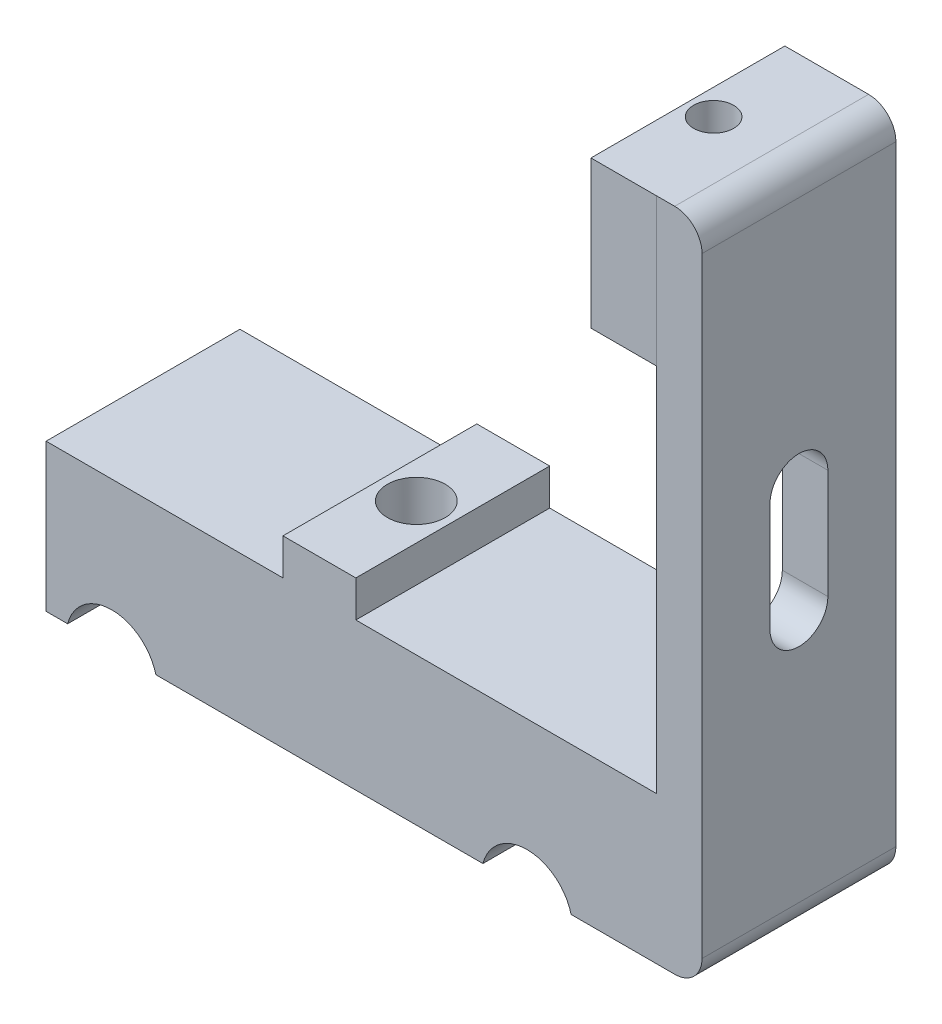
SolidWorks part; units mm, degrees
ref_plane "Front Plane" through (0, 0, 0) normal (0, 0, 1) x (1, 0, 0)
ref_plane "Top Plane" through (0, 0, 0) normal (0, 1, 0) x (1, 0, 0)
ref_plane "Right Plane" through (0, 0, 0) normal (1, 0, 0) x (0, 0, -1)
sketch "Sketch2" plane through (0, 0, 0) normal (0, 0, 1) x (1, 0, 0)
  line L0 (10.1, 0) -> (-10.1, 0)
  line L1 (-10.1, 0) -> (-10.1, 1.7099)
  line L2 (-10.1, 1.7099) -> (-6.2548, 7)
  line L3 (-6.2548, 7) -> (6.2548, 7)
  line L4 (0, 7) -> (0, 0)
  line L5 (0, 0) -> (0, 9.2516) construction
  line L6 (10.1, 1.7099) -> (6.2548, 7)
  line L7 (10.1, 0) -> (10.1, 1.7099)
  dimension "D1" = 20.2
  dimension "D2" = 7
extrude "Boss-Extrude1" add sketch "Sketch2" along normal blind 10.8 contours L4 L3 L2 L1 L0 | L0 L7 L6 L3 L4 region at (4.4168, 3.2082, 0) region at (-4.4168, 3.2082, 0)
sketch "Sketch4" plane through (0, 0, 0) normal (0, 0, 1) x (1, 0, 0)
  line L0 (-4, 0) -> (-4, -4.8)
  line L1 (10.1, 0) -> (-10.1, 0) construction
  line L2 (-4, -4.8) -> (-30, -4.8)
  line L3 (-30, -4.8) -> (-30, -29.8)
  line L4 (-30, -29.8) -> (30, -29.8)
  line L5 (0, 0) -> (0, -29.8) construction
  line L6 (0, -29.8) -> (0, 0)
  line L7 (4, 0) -> (-4, 0)
  line L8 (0, 0) -> (0, -30.5381) construction
  line L9 (30, -4.8) -> (30, -29.8)
  line L10 (4, -4.8) -> (30, -4.8)
  line L11 (4, 0) -> (4, -4.8)
  line L13 (-30, -20.98) -> (30, -20.98)
  line L14 (-30, -20.98) -> (-30, -23.48)
  line L15 (-30, -23.48) -> (30, -23.48)
  line L16 (30, -20.98) -> (30, -23.48)
  dimension "D1" = 4.8
  dimension "D2" = 4
  dimension "D3" = 25
  dimension "D4" = 60
  dimension "D6" = 8.82
extrude "Boss-Extrude2" add sketch "Sketch4" along normal mid plane 21.28 contours L6 L7 L0 L2 L3 L4 | L11 L7 L6 L4 L9 L10 region at (-14.5054, -12.4909, 0) region at (14.5054, -12.4909, 0)
sketch "Sketch5" plane through (0, 0, 0) normal (0, 0, 1) x (1, 0, 0)
  line L0 (-29.791, -22.2274) -> (26.9734, -22.2274) construction
  line L3 (0, -20.98) -> (0, 7) construction
  line L5 (-6.2548, 7) -> (6.2548, 7) construction
  line L20 (-30, -20.98) -> (30, -20.98) construction
  circle A0 centre (-22.791, -22.2274) radius 5
  circle A1 centre (22.791, -22.2274) radius 5
  dimension "D1" = 7
extrude "Cut-Extrude1" cut sketch "Sketch5" along normal through all both and the other way through all
fillet "Fillet1" radius 1 6 edges at (-10.1, 0, 5.4) (-10.1, 1.7099, 5.4) (-6.2548, 7, 5.4) (6.2548, 7, 5.4) (10.1, 0, 5.4) (10.1, 1.7099, 5.4)
sketch "Sketch6" plane through (30, 0, 0) normal (1, 0, 0) x (0, 0, -1)
  line L0 (-10.64, -20.98) -> (10.64, -20.98) construction
  line L1 (-10.64, -4.8) -> (10.64, -4.8)
  line L2 (-10.64, -4.8) -> (-10.64, -20.98)
  line L3 (-10.64, -20.98) -> (10.64, -20.98)
  line L4 (10.64, -4.8) -> (10.64, -20.98)
extrude "Boss-Extrude3" add sketch "Sketch6" along normal blind 12
sketch "Sketch7" plane through (0, -4.8, 0) normal (0, 1, 0) x (1, 0, 0)
  line L0 (4, -10.64) -> (42, -10.64) construction
  line L1 (42, 10.6413) -> (37, 10.6413)
  line L2 (42, 10.6413) -> (42, -10.64)
  line L3 (42, -10.64) -> (37, -10.64)
  line L4 (37, 10.6413) -> (37, -10.64)
  dimension "D1" = 5
extrude "Boss-Extrude4" add sketch "Sketch7" along normal blind 56.83
sketch "Sketch8" plane through (37, 0, 0) normal (-1, 0, 0) x (0, 0, 1)
  line L0 (-10.6413, 52.03) -> (-10.6413, -4.8) construction
  line L1 (10.643, 52.03) -> (-10.6413, 52.03)
  line L2 (10.643, 52.03) -> (10.643, 35.85)
  line L3 (10.643, 35.85) -> (-10.6413, 35.85)
  line L4 (-10.6413, 52.03) -> (-10.6413, 35.85)
  dimension "D1" = 16.18
extrude "Boss-Extrude5" add sketch "Sketch8" along normal blind 7.19
fillet "Fillet3" radius 3 2 edges at (42, 52.03, -0.0007) (42, -20.98, 0)
sketch "Sketch9" plane through (0, -20.98, 0) normal (0, -1, 0) x (1, 0, 0)
  line L0 (27.6329, 0) -> (27.6329, 10.8) construction
  line L2 (27.6329, 10.64) -> (39, 10.64) construction
  circle A0 centre (32.6329, 0) radius 2.2
  dimension "D1" = 5
  dimension "D2" = 10.64
extrude "Cut-Extrude2" cut sketch "Sketch9" against normal through all
sketch "Sketch10" plane through (0, -20.98, 0) normal (0, -1, 0) x (1, 0, 0)
  line L2 (-17.9491, 0) -> (-17.9491, 10.8) construction
  line L3 (-17.9491, 10.64) -> (17.9491, 10.64) construction
  circle A0 centre (0.0009, 0) radius 3.175
  dimension "D1" = 10.64
  dimension "D3" = 6.35
  dimension "D2" = 17.95
extrude "Cut-Extrude3" cut sketch "Sketch10" against normal through all
sketch "Sketch11" plane through (0, 0, 10.8) normal (0, 0, 1) x (1, 0, 0)
  line L0 (9.1, 0) -> (-9.1, 0) construction
  line L1 (-12.6098, 8.9215) -> (12.3675, 8.9215)
  line L2 (-12.6098, 8.9215) -> (-12.6098, -0.8)
  line L3 (-12.6098, -0.8) -> (12.3675, -0.8)
  line L4 (12.3675, 8.9215) -> (12.3675, -0.8)
  dimension "D1" = 0.8
extrude "Cut-Extrude4" cut sketch "Sketch11" against normal through all
sketch "Sketch12" plane through (42, 0, 0) normal (1, 0, 0) x (0, 0, -1)
  line L0 (-3.175, 21.525) -> (-3.175, 9.525)
  line L1 (10.6413, 49.03) -> (-10.64, 49.03) construction
  line L2 (3.175, 9.525) -> (3.175, 21.525)
  arc A0 (3.175, 21.525) -> (-3.175, 21.525) centre (0, 21.525) ccw
  arc A1 (-3.175, 9.525) -> (3.175, 9.525) centre (0, 9.525) ccw
  dimension "D1" = 27.505
  dimension "D2" = 12
extrude "Cut-Extrude5" cut sketch "Sketch12" against normal through all
sketch "Sketch13" plane through (0, 0, 10.643) normal (0, 0, 1) x (1, 0, 0)
  line L1 (29.81, 52.03) -> (49.81, 52.03)
  line L2 (29.81, 52.03) -> (29.81, 35.85)
  line L3 (29.81, 35.85) -> (49.81, 35.85)
  line L4 (49.81, 52.03) -> (49.81, 35.85)
  dimension "D1" = 20
extrude "Boss-Extrude6" [suppressed] add sketch "Sketch13" along normal blind 18.2
sketch "Sketch14" [suppressed] plane through (0, 52.03, 0) normal (0, 1, 0) x (1, 0, 0)
  line L0 (49.81, -28.843) -> (49.81, -10.643) construction
  line L1 (49.81, -28.843) -> (29.81, -28.843) construction
  line L2 (29.81, -18.643) -> (49.81, -18.643) construction
  line L3 (29.81, -28.843) -> (29.81, 10.6413) construction
  circle A0 centre (35.31, -21.643) radius 1.275
  circle A1 centre (44.81, -21.643) radius 1.275
  dimension "D1" = 14.5
  dimension "D2" = 9.5
  dimension "D3" = 3
  dimension "D4" = 10.2
extrude "Cut-Extrude6" [suppressed] cut sketch "Sketch14" against normal through all
